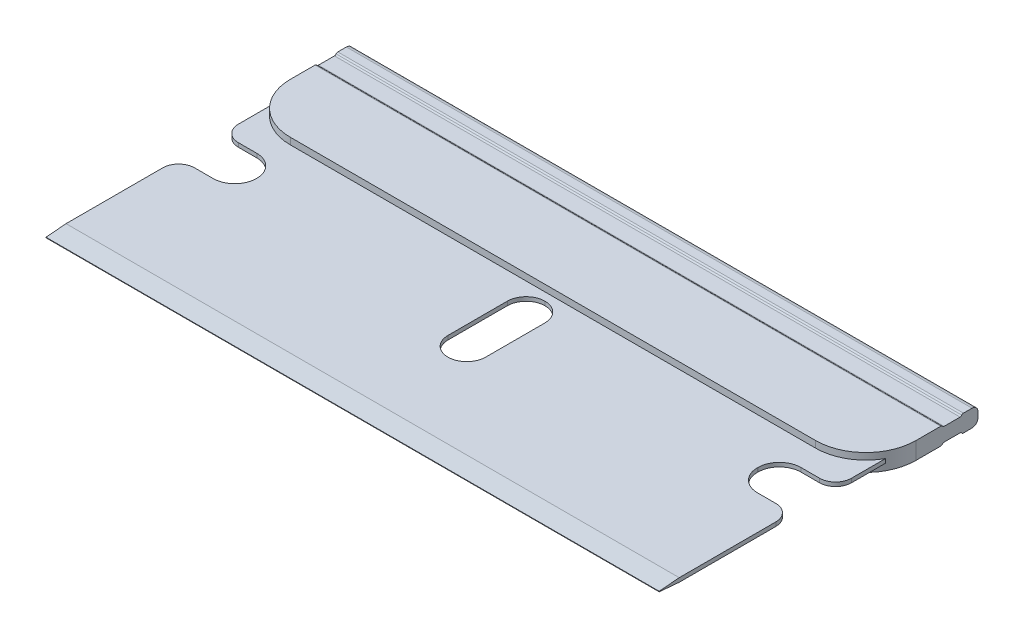
SolidWorks part; units mm, degrees
ref_plane "Front" through (0, 0, 0) normal (0, 0, 1) x (1, 0, 0)
ref_plane "Top" through (0, 0, 0) normal (0, 1, 0) x (1, 0, 0)
ref_plane "Right" through (0, 0, 0) normal (1, 0, 0) x (0, 0, -1)
sketch "Sketch1" plane through (0, 0, 0) normal (0, 1, 0) x (1, 0, 0)
  line L1 (-82.6935, -3.0635) -> (-43.8315, -3.0635)
  line L2 (-82.6935, -3.0635) -> (-82.6935, -22.8755)
  line L3 (-82.6935, -22.8755) -> (-43.8315, -22.8755)
  line L4 (-43.8315, -3.0635) -> (-43.8315, -22.8755)
extrude "Boss-Extrude1" add sketch "Sketch1" along normal blind 0.254
chamfer "Chamfer1" distance 1.27 angle 5 1 edges at (-63.2625, 0.254, 22.8755) first distance on face at (-63.2625, 0.254, 12.9695)
chamfer "Chamfer2" distance 1.27 angle 5 1 edges at (-63.2625, 0, 22.8755) first distance on face at (-63.2625, 0, 12.9695)
sketch "Sketch2" plane through (0, 0.254, 0) normal (0, 1, 0) x (-1, 0, 0)
  line L0 (43.8315, 21.6055) -> (43.8315, 3.0635) construction
  line L1 (82.6935, 3.0635) -> (43.8315, 3.0635)
  line L2 (82.6935, 3.0635) -> (82.6935, 10.1755)
  line L3 (82.6935, 10.1755) -> (43.8315, 10.1755)
  line L4 (43.8315, 3.0635) -> (43.8315, 10.1755)
extrude "Boss-Extrude2" add sketch "Sketch2" along normal blind 1.0922 separate body
move or copy body "Body-Move/Copy1" bodies to move or copy 102 copy no translate (0, -0.6731, 0)
other "Move Face1" face at (-82.6935, 0.127, 6.6195) face at (-43.8315, 0.127, 6.6195) offset 0.3937 parameters "D1"=0.3937
fillet "Fillet1" radius 3.175 2 edges at (-43.4378, 0.127, 10.1755) (-83.0872, 0.127, 10.1755)
combine bodies "Combine1" operation type add bodies to combine 101 103
fillet "Fillet2" radius 0.381 2 edges at (-63.2625, -0.4191, 3.0635) (-63.2625, 0.6731, 3.0635)
sketch "Sketch3" plane through (-43.4378, 0, 0) normal (1, 0, 0) x (0, 0, -1)
  line L3 (-4.0719, -0.3075) -> (-5.3419, -0.3075)
  line L4 (-4.0719, 0.5615) -> (-5.3419, 0.5615)
  line L5 (-5.3419, 0.5615) -> (-5.3419, 1.2042)
  line L6 (-5.3419, 1.2042) -> (-4.0719, 1.2042)
  line L7 (-4.0719, 1.2042) -> (-4.0719, 0.5615)
  line L8 (-4.0719, -0.9502) -> (-4.0719, -0.3075)
  line L9 (-5.3419, -0.9502) -> (-4.0719, -0.9502)
  line L10 (-5.3419, -0.3075) -> (-5.3419, -0.9502)
extrude "Cut-Extrude1" cut sketch "Sketch3" against normal through all
fillet "Fillet3" radius 0.127 4 edges at (-63.2625, -0.3075, 5.3419) (-63.2625, -0.3075, 4.0719) (-63.2625, 0.5615, 5.3419) (-63.2625, 0.5615, 4.0719)
fillet "Fillet4" radius 0.127 4 edges at (-63.2625, -0.4191, 4.0719) (-63.2625, -0.4191, 5.3419) (-63.2625, 0.6731, 5.3419) (-63.2625, 0.6731, 4.0719)
sketch "Sketch4" plane through (0, 0.254, 0) normal (0, 1, 0) x (-1, 0, 0)
  line L2 (82.6935, 11.6995) -> (79.1375, 11.6995)
  line L3 (82.6935, 8.5318) -> (82.6935, 21.6055) construction
  line L4 (79.1375, 11.6995) -> (79.1375, 14.4681)
  line L5 (79.1375, 14.4681) -> (84.3444, 14.4681)
  line L6 (84.3444, 14.4681) -> (84.3444, 11.6995)
  line L7 (84.3444, 11.6995) -> (82.6935, 11.6995)
  line L9 (47.3875, 14.4681) -> (42.1806, 14.4681)
  line L10 (47.3875, 11.6995) -> (47.3875, 14.4681)
  line L11 (43.8315, 11.6995) -> (47.3875, 11.6995)
  line L12 (42.1806, 11.6995) -> (43.8315, 11.6995)
  line L13 (42.1806, 14.4681) -> (42.1806, 11.6995)
extrude "Cut-Extrude2" cut sketch "Sketch4" against normal through all
fillet "Fillet5" radius 1.3716 4 edges at (-47.3875, 0.127, 11.6995) (-47.3875, 0.127, 14.4681) (-79.1375, 0.127, 14.4681) (-79.1375, 0.127, 11.6995)
fillet "Fillet6" radius 1.016 4 edges at (-82.6935, 0.127, 14.4681) (-82.6935, 0.127, 11.6995) (-43.8315, 0.127, 14.4681) (-43.8315, 0.127, 11.6995)
sketch "Sketch5" plane through (0, 0.254, 0) normal (0, 1, 0) x (1, 0, 0)
  line L0 (-62.0687, -10.6835) -> (-62.0687, -16.8303)
  line L2 (-62.0687, -10.6835) -> (-64.4563, -10.6835)
  line L3 (-64.4563, -10.6835) -> (-64.4563, -16.8303)
  line L4 (-64.4563, -16.8303) -> (-62.0687, -16.8303)
  point P3 (-63.2625, -10.6835)
extrude "Cut-Extrude3" cut sketch "Sketch5" against normal through all
fillet "Fillet7" radius 1.1938 4 edges at (-64.4563, 0.127, 16.8303) (-62.0687, 0.127, 16.8303) (-62.0687, 0.127, 10.6835) (-64.4563, 0.127, 10.6835)
